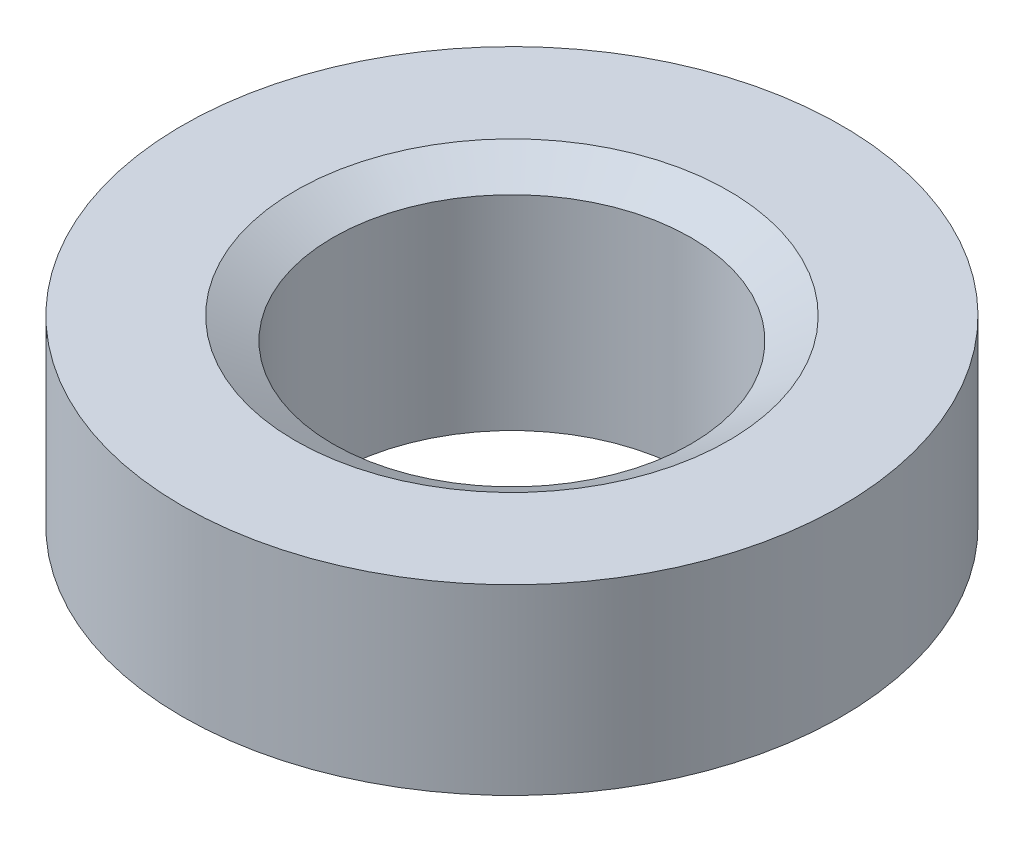
SolidWorks part; units mm, degrees
ref_plane "Front Plane" through (0, 0, 0) normal (0, 0, 1) x (1, 0, 0)
ref_plane "Top Plane" through (0, 0, 0) normal (0, 1, 0) x (1, 0, 0)
ref_plane "Right Plane" through (0, 0, 0) normal (1, 0, 0) x (0, 0, -1)
sketch "Sketch1" plane through (0, 0, 0) normal (0, 1, 0) x (1, 0, 0)
  circle A0 centre (0, 0) radius 2.375
  circle A1 centre (0, 0) radius 4.375
  dimension "D1" = 4.75
  dimension "D2" = 2
extrude "Boss-Extrude1" add sketch "Sketch1" along normal blind 3
chamfer "Chamfer1" distance 0.5 angle 30 1 edges at (0, 3, 2.375) first distance on face at (0, 3, 4.375)
chamfer "Chamfer2" distance 1 angle 30 1 edges at (0, 0, 4.375) first distance on face at (0, 0, 4.375)
